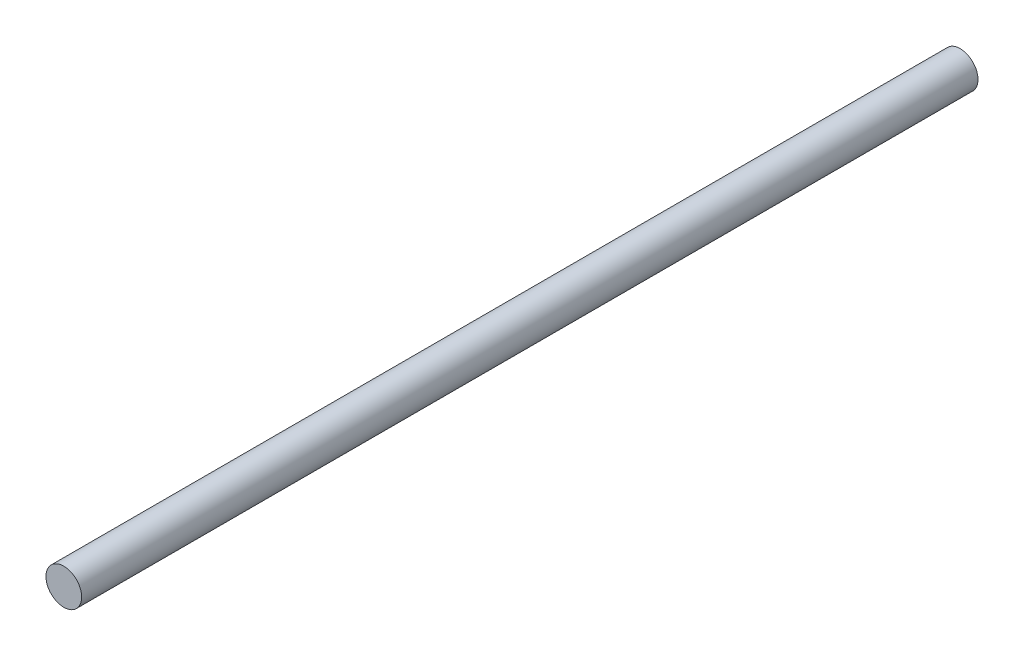
SolidWorks part; units mm, degrees
material "201 Annealed Stainless Steel (SS)"
ref_plane "Front Plane" through (0, 0, 0) normal (0, 0, 1) x (1, 0, 0)
ref_plane "Top Plane" through (0, 0, 0) normal (0, 1, 0) x (1, 0, 0)
ref_plane "Right Plane" through (0, 0, 0) normal (1, 0, 0) x (0, 0, -1)
sketch "Sketch1" plane through (0, 0, 0) normal (0, 0, 1) x (1, 0, 0)
  circle A0 centre (0, 0) radius 2.3813
  dimension "D1" = 4.7625
extrude "Boss-Extrude1" add sketch "Sketch1" along normal blind 119.6848
sketch "Sketch2" plane through (0, 0, 0) normal (0, 0, -1) x (-1, 0, 0)
  circle A0 centre (0, 0) radius 1.5875
  circle A1 centre (0, 0) radius 2.3813
  dimension "D1" = 3.175
extrude "Cut-Extrude1" [suppressed] cut sketch "Sketch2" against normal blind 12.7
sketch "Sketch3" plane through (0, 0, 119.6848) normal (0, 0, 1) x (1, 0, 0)
  circle A0 centre (0, 0) radius 1.5875
  circle A1 centre (0, 0) radius 2.3813
  dimension "D1" = 3.175
extrude "Cut-Extrude2" [suppressed] cut sketch "Sketch3" against normal blind 12.7
